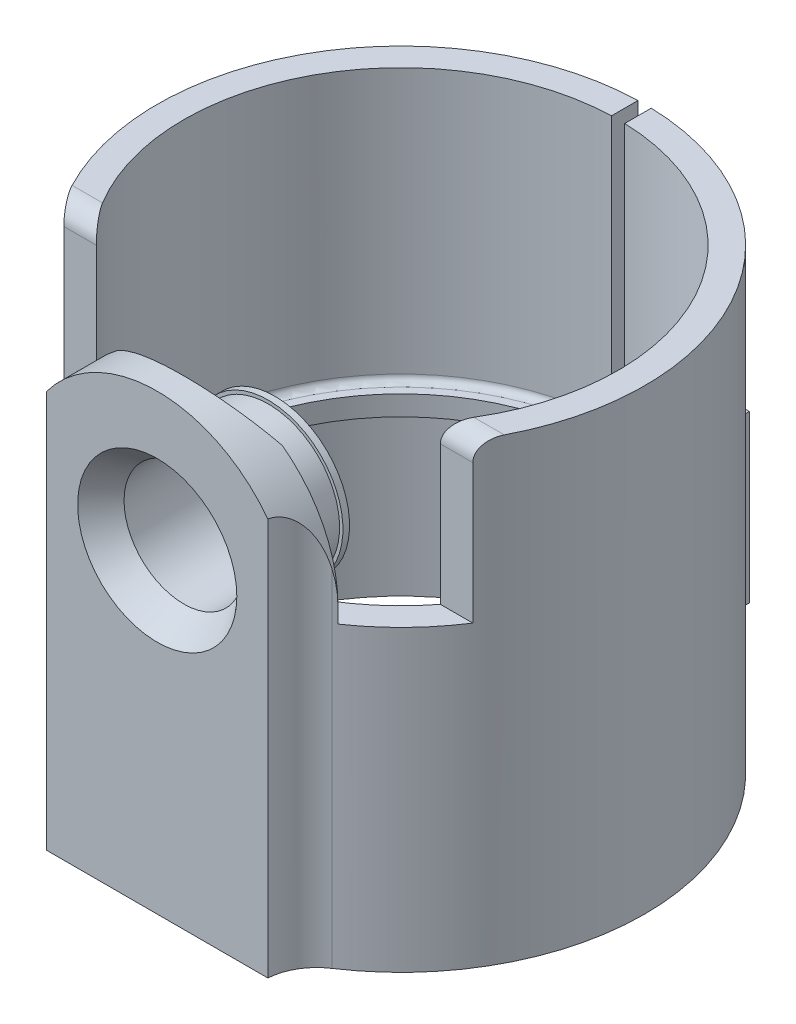
SolidWorks part; units mm, degrees
ref_plane "Спереди" through (0, 0, 0) normal (0, 0, 1) x (1, 0, 0)
ref_plane "Сверху" through (0, 0, 0) normal (0, 1, 0) x (1, 0, 0)
ref_plane "Справа" through (0, 0, 0) normal (1, 0, 0) x (0, 0, -1)
sketch "Эскиз1" plane through (0, 0, 0) normal (0, 1, 0) x (1, 0, 0)
  line L0 (0, 0) -> (0, -43.0119) construction
  line L2 (-16.6733, -36.75) -> (16.6733, -36.75)
  line L3 (-16.6733, -36.75) -> (-16.6733, -32.75)
  line L5 (16.6733, -36.75) -> (16.6733, -32.75)
  arc A0 (-16.6733, -32.75) -> (16.6733, -32.75) centre (0, 0) cw
  circle A1 centre (0, 0) radius 32.75
  dimension "D1" = 65.5
  dimension "D2" = 36.75
  dimension "D3" = 4
extrude "main" add sketch "Эскиз1" along normal blind 44 and the other way blind 25
sketch "Эскиз2" plane through (0, 0, 0) normal (0, 0, 1) x (1, 0, 0)
  circle A0 centre (0, 22.5) radius 11
  dimension "D1" = 22
  dimension "D2" = 22.5
extrude "hole" cut sketch "Эскиз2" along normal through all
sketch "Эскиз3" plane through (0, 0, 0) normal (0, 1, 0) x (1, 0, 0)
  circle A0 centre (0, 0) radius 32.75
  circle A1 centre (0, 0) radius 30.5
  circle A3 centre (0, 0) radius 32.75 construction
  dimension "D1" = 61
extrude "stop" add sketch "Эскиз3" along normal blind 3
sketch "Эскиз4" plane through (0, 0, 0) normal (0, 1, 0) x (1, 0, 0)
  line L0 (4, 36.5317) -> (0, 0) construction
  line L1 (0, 0) -> (-4, 36.5317) construction
  line L2 (0, 0) -> (0, 39.0687) construction
  line L3 (-4, 36.5317) -> (-4, 48.5317)
  line L4 (-4, 48.5317) -> (4, 48.5317)
  line L5 (4, 48.5317) -> (4, 36.5317)
  arc A0 (-4, 36.5317) -> (4, 36.5317) centre (0, 0) cw
  arc A1 (16.6733, -32.75) -> (-16.6733, -32.75) centre (0, 0) ccw construction
  dimension "D1" = 4
  dimension "D2" = 4
  dimension "D3" = 12
extrude "lock" add sketch "Эскиз4" against normal up to surface (25 mm away) up to face at (0, -25, 32.75)
sketch "Эскиз5" plane through (0, 0, 0) normal (0, 1, 0) x (1, 0, 0)
  line L0 (4, 48.5317) -> (-4, 48.5317) construction
  line L1 (-1, 0) -> (1, 0)
  line L2 (-1, 0) -> (-1, 48.5317)
  line L3 (-1, 48.5317) -> (1, 48.5317)
  line L4 (1, 0) -> (1, 48.5317)
  dimension "D1" = 1
extrude "slot" cut sketch "Эскиз5" against normal through all and the other way through all
sketch "Эскиз6" plane through (4, 0, 0) normal (1, 0, 0) x (0, 0, -1)
  line L0 (42.5317, 7.5457) -> (42.5317, -34.4595) construction
  line L1 (48.5317, -25) -> (36.5317, -25) construction
  line L2 (40.425, 0) -> (-40.425, 0) construction
  circle A0 centre (42.5317, -7) radius 2.5
  circle A1 centre (42.5317, -18) radius 2.5
  point P4 (42.5317, -25)
  dimension "D1" = 5
  dimension "D2" = 5
  dimension "D3" = 7
  dimension "D4" = 7
extrude "small holes" cut sketch "Эскиз6" against normal through all
ref_plane "Плоскость1" through (0, 0, 20) normal (0, 0, 1) x (1, 0, 0)
sketch "Эскиз10" plane through (0, 0, 0) normal (1, 0, 0) x (0, 0, -1)
  line L0 (-20, 40.425) -> (-20, -40.425) construction
  line L1 (-20, 20.0487) -> (-30.3, 20.0487)
  line L2 (-20, 20.0487) -> (-20, 60)
  line L3 (-20, 60) -> (-30.3, 60)
  line L4 (-30.3, 20.0487) -> (-30.3, 60)
  dimension "D1" = 10.3
extrude "key slot" cut sketch "Эскиз10" against normal through all and the other way through all
sketch "Эскиз9" plane through (0, 0, 20) normal (0, 0, 1) x (1, 0, 0)
  circle A0 centre (0, 22.5) radius 9
  circle A1 centre (0, 22.5) radius 11
  dimension "D2" = 18
  dimension "D3" = 22
  dimension "D1" = 22.5
extrude "tube" add sketch "Эскиз9" along normal up to surface (16.75 mm away) up to face at (0, 9.5, 36.75)
sketch "Эскиз11" plane through (0, 0, 20) normal (0, 0, -1) x (-1, 0, 0)
  circle A0 centre (0, 22.5) radius 13
  circle A2 centre (0, 22.5) radius 10.75
  circle A3 centre (0, 22.5) radius 9 construction
  dimension "D1" = 21.5
  dimension "D2" = 26
extrude "tube slot" cut sketch "Эскиз11" against normal up to surface (10.3 mm away) up to face at (-16.6123, 32.0244, 30.3)
chamfer "Фаска1" distance 3 distance2 4 1 edges at (9, 22.5, 36.75) first distance on face at (0, 9.5, 36.75)
sketch "Эскиз12" plane through (0, 0, 20) normal (0, 0, -1) x (-1, 0, 0)
  circle A0 centre (0, 22.5) radius 11.25
  circle A1 centre (0, 22.5) radius 9
  circle A2 centre (0, 22.5) radius 9 construction
  dimension "D1" = 22.5
extrude "tube stop" add sketch "Эскиз12" along normal blind 1
sketch "Эскиз14" plane through (0, 0, 20) normal (0, 0, 1) x (1, 0, 0)
  line L2 (-20.796, 22.5) -> (-20.796, 44)
  line L3 (-20.796, 44) -> (20.796, 44)
  line L4 (20.796, 44) -> (20.796, 22.5)
  arc A0 (-20.796, 22.5) -> (20.796, 22.5) centre (0, 22.5) cw
  circle A2 centre (0, 22.5) radius 11 construction
extrude "tube external" cut sketch "Эскиз14" along normal through all
fillet "Скругление3" radius 8 2 edges at (-16.6733, 4.9643, 32.75) (16.6733, 4.9643, 32.75)
fillet "Скругление5" radius 1 1 edges at (0, 3, 32.75)
fillet "Скругление6" radius 1 2 edges at (4, -12.5, -36.5317) (-4, -12.5, -36.5317)
fillet "Скругление7" radius 3 2 edges at (28.3825, 44, 20) (-28.3825, 44, 20)
